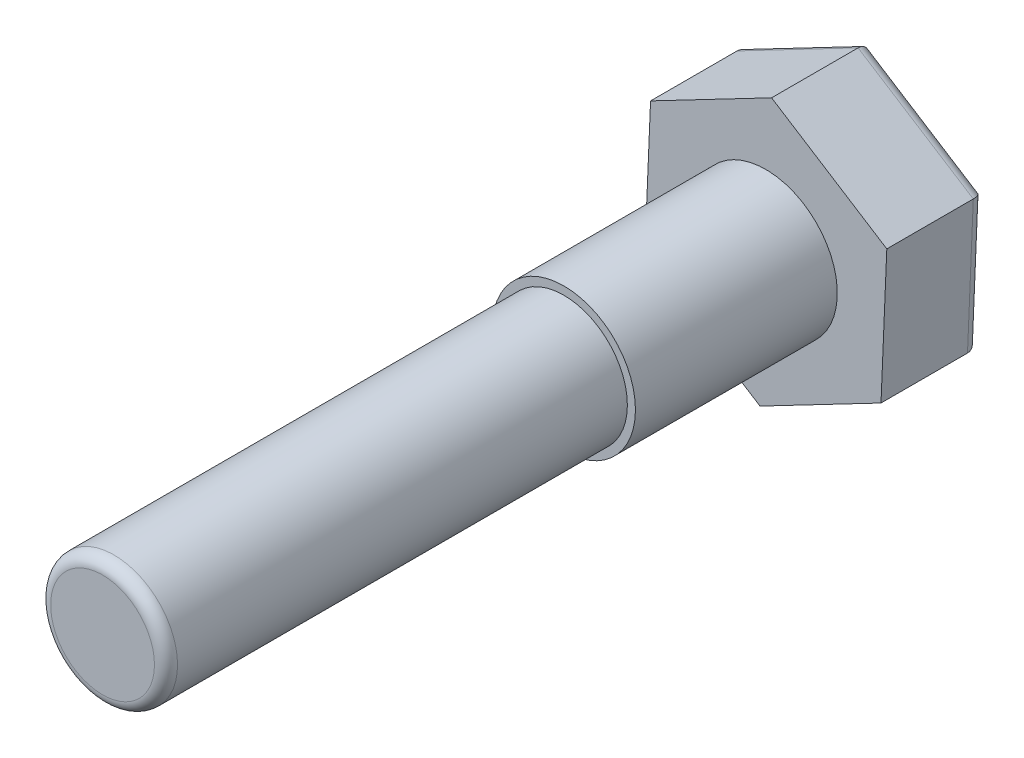
SolidWorks part; units mm, degrees
ref_plane "前视" through (0, 0, 0) normal (0, 0, 1) x (1, 0, 0)
ref_plane "上视" through (0, 0, 0) normal (0, 1, 0) x (1, 0, 0)
ref_plane "右视" through (0, 0, 0) normal (1, 0, 0) x (0, 0, -1)
sketch "草图1" plane through (0, 0, 0) normal (0, 0, 1) x (1, 0, 0)
  line L1 (20.9842, 10.9543) -> (1.0054, 23.65)
  line L2 (1.0054, 23.65) -> (-19.9788, 12.6957)
  line L3 (-19.9788, 12.6957) -> (-20.9842, -10.9543)
  line L4 (-20.9842, -10.9543) -> (-1.0054, -23.65)
  line L5 (-1.0054, -23.65) -> (19.9788, -12.6957)
  line L6 (19.9788, -12.6957) -> (20.9842, 10.9543)
  circle A0 centre (0, 0) radius 20.5 construction
  dimension "D1" = 47.3
  dimension "D2" = 41
extrude "基体-拉伸" add sketch "草图1" along normal blind 17
sketch "草图2" plane through (0, 0, 17) normal (0, 0, 1) x (1, 0, 0)
  circle A0 centre (0, 0) radius 12.4
  dimension "D1" = 24.8
extrude "凸台-拉伸1" add sketch "草图2" along normal blind 35
fillet "圆角3" radius 2 6 edges at (10.9948, 17.3021, 0) (-9.4867, 18.1729, 0) (-20.4815, 0.8707, 0) (-10.9948, -17.3021, 0) (9.4867, -18.1729, 0) (20.4815, -0.8707, 0)
sketch "草图3" plane through (0, 0, 52) normal (0, 0, 1) x (1, 0, 0)
  circle A0 centre (0, 0) radius 11
  dimension "D1" = 22
extrude "凸台-拉伸2" add sketch "草图3" along normal blind 80
fillet "圆角4" radius 2 1 edges at (11, 0, 132)
